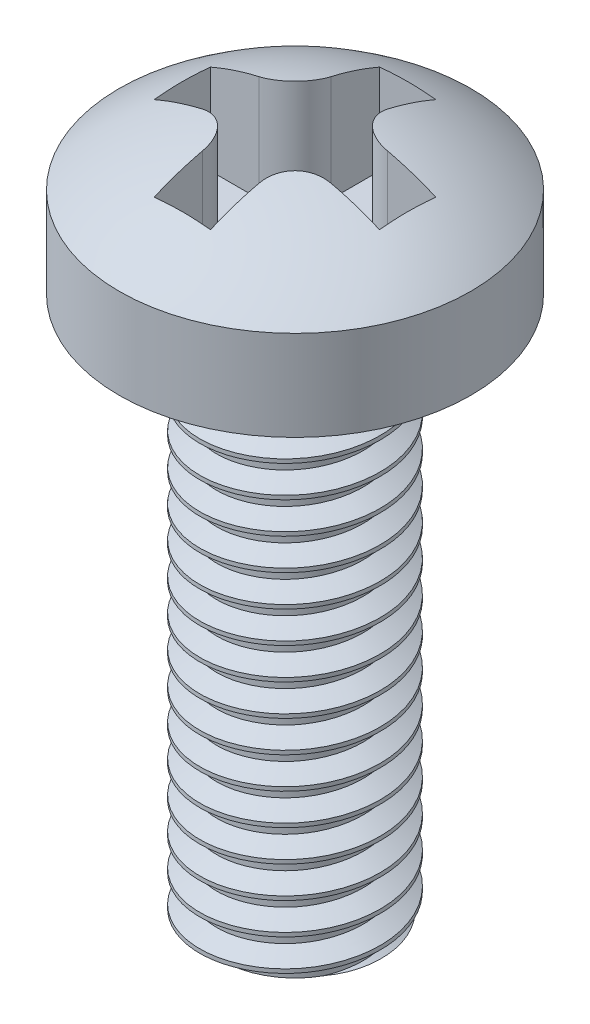
SolidWorks part; units mm, degrees
ref_plane "Front Plane" through (0, 0, 0) normal (0, 0, 1) x (1, 0, 0)
ref_plane "Top Plane" through (0, 0, 0) normal (0, 1, 0) x (1, 0, 0)
ref_plane "Right Plane" through (0, 0, 0) normal (1, 0, 0) x (0, 0, -1)
sketch "Sketch1" plane through (0, 0, 0) normal (0, 1, 0) x (1, 0, 0)
  circle A0 centre (0, 0) radius 2
  dimension "D1" = 4
extrude "Boss-Extrude1" add sketch "Sketch1" along normal blind 12
thread "Thread1" pitch 0.7 method cut profile "Thread Profile1" start angle 0, offset 0, length 12, pitch 0.7, diameter 4
ref_plane "Plane1" through (-2, 12, 0) normal (0, 0, 1) x (-1, 0, 0)
sketch "Thread Profile1" plane through (-2, 12, 0) normal (0, 0, 1) x (-1, 0, 0)
  line L0 (0, 0) -> (0, 0.7) construction
  line L11 (0, 0) -> (0, 0.6125)
  line L12 (0, 0.6125) -> (-0.3789, 0.3937)
  line L13 (-0.3789, 0.3937) -> (-0.3789, 0.2187)
  line L15 (-0.3789, 0.2187) -> (0, 0)
  line L17 (-0.3789, 0.3062) -> (0, 0.3062) construction
  point P2 (0, 0)
  dimension "Pitch" = 0.7
  dimension "Profile_Angle" = 60
  dimension "Profile_Land" = 0.175
  dimension "Profile_Height" = 0.3789
sketch "Sketch5" plane through (0, 12, 0) normal (0, 1, 0) x (1, 0, 0)
  circle A0 centre (0, 0) radius 3.9
  dimension "D1" = 7.8
extrude "Boss-Extrude2" add sketch "Sketch5" along normal blind 2
sketch "Sketch6" plane through (0, 0, 0) normal (1, 0, 0) x (0, 0, -1)
  line L0 (3.9, 14) -> (-3.9, 14) construction
  line L1 (0, 15.346) -> (0, 14)
  line L2 (3.9, 14) -> (0, 14)
  arc A0 (3.9, 14) -> (0, 15.346) centre (0, 9.0227) ccw
  point P3 (2.0629, 15)
  dimension "D1" = 1
revolve "Revolve1" add sketch "Sketch6" angle 360 about L1
ref_plane "Plane2" through (0, 15.346, 0) normal (0, 1, 0) x (1, 0, 0)
sketch "Sketch7" plane through (0, 15.346, 0) normal (0, 1, 0) x (1, 0, 0)
  line L0 (-2.5, 0) -> (2.5, 0) construction
  line L1 (0, 2.5) -> (0, -2.5) construction
  line L2 (-2.5, -0.625) -> (-1.425, -0.625)
  line L3 (-0.625, 2.5) -> (-0.625, 1.425)
  line L4 (-2.5, 0.625) -> (-1.425, 0.625)
  line L5 (0.625, 2.5) -> (0.625, 1.425)
  line L6 (2.5, 0.625) -> (2.5, -0.625)
  line L7 (0.625, -2.5) -> (-0.625, -2.5)
  line L8 (-2.5, 0.625) -> (-2.5, -0.625)
  line L9 (0.625, 2.5) -> (-0.625, 2.5)
  line L10 (1.425, 0.625) -> (2.5, 0.625)
  line L11 (-2.5, 0.625) -> (2.5, 0.625) construction
  line L12 (0.625, -1.425) -> (0.625, -2.5)
  line L13 (0.625, 2.5) -> (0.625, -2.5) construction
  line L14 (1.425, -0.625) -> (2.5, -0.625)
  line L15 (-2.5, -0.625) -> (2.5, -0.625) construction
  line L16 (-0.625, -1.425) -> (-0.625, -2.5)
  line L17 (-0.625, 2.5) -> (-0.625, -2.5) construction
  arc A0 (-1.425, 0.625) -> (-0.625, 1.425) centre (-1.425, 1.425) ccw
  arc A1 (-1.425, -0.625) -> (-0.625, -1.425) centre (-1.425, -1.425) cw
  arc A2 (0.625, -1.425) -> (1.425, -0.625) centre (1.425, -1.425) cw
  arc A3 (1.425, 0.625) -> (0.625, 1.425) centre (1.425, 1.425) cw
  point P4 (0, 0)
  point P8 (0, 0)
  point P24 (-0.625, -0.625)
  point P27 (0.625, -0.625)
  dimension "D4" = 0.8
  dimension "D1" = 5
  dimension "D2" = 0.625
  dimension "D3" = 0.625
extrude "Cut-Extrude1" cut sketch "Sketch7" against normal offset from surface (2.546 mm away) 0.8 up to face at (0, 12, 3.9)
